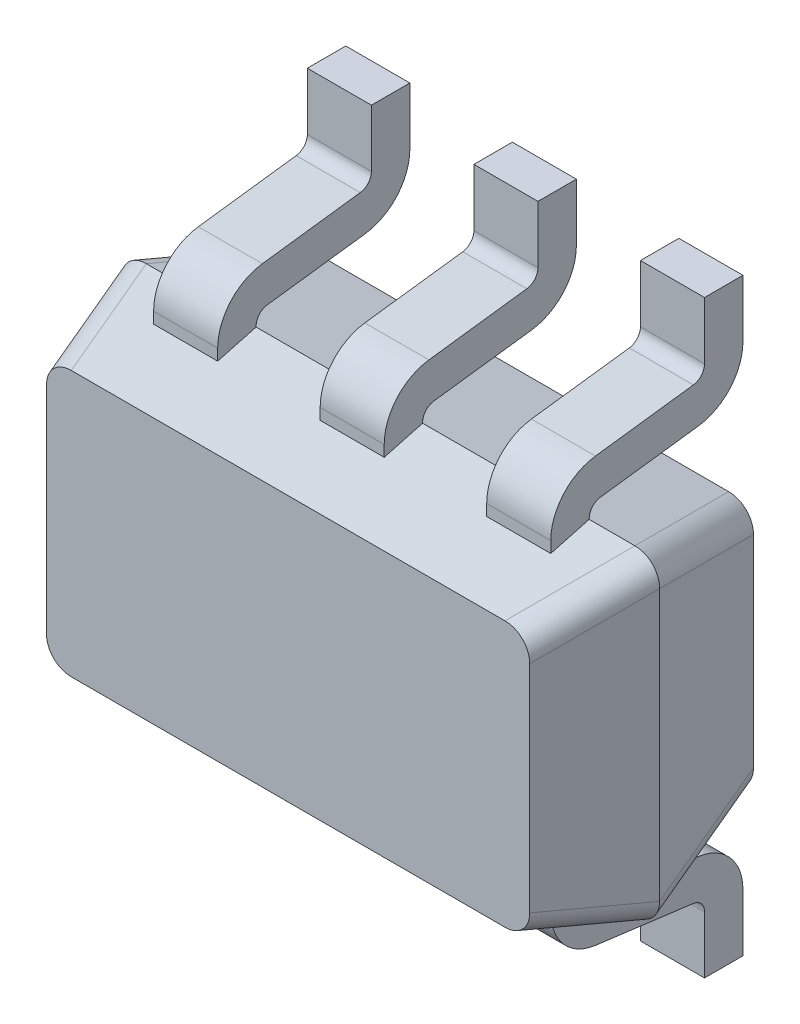
SolidWorks part; units mm, degrees
note: The reader was unsure of these and kept them because the rebuilt part matched: shared geometry of "Эскиз2<4>".
ref_plane "Спереди" through (0, 0, 0) normal (0, 0, 1) x (1, 0, 0)
ref_plane "Сверху" through (0, 0, 0) normal (0, 1, 0) x (1, 0, 0)
ref_plane "Справа" through (0, 0, 0) normal (1, 0, 0) x (0, 0, -1)
sketch "Эскиз1" plane through (0, 0, 0) normal (0, 0, 1) x (1, 0, 0)
  line L1 (-1.05, 0.625) -> (1.05, 0.625)
  line L2 (-1.05, 0.625) -> (-1.05, -0.625)
  line L3 (-1.05, -0.625) -> (1.05, -0.625)
  line L4 (1.05, 0.625) -> (1.05, -0.625)
  point P0 (0, 0)
extrude "Вытянуть1" add sketch "Эскиз1" along normal blind 0.4 draft 15 and the other way blind 0.5 draft 15 from offset 0.6
sketch "Эскиз2" plane through (0, 0, 0) normal (1, 0, 0) x (0, 0, -1)
  line L0 (-0.15, -1.15) -> (0, -1.15)
  line L1 (0, -1.15) -> (0, -0.9259)
  line L2 (-0.75, -0.55) -> (-0.75, -0.6286)
  line L3 (-0.6, -0.6286) -> (-0.6, -0.55)
  line L4 (-0.5564, -0.6782) -> (-0.1744, -0.7275)
  line L5 (-0.15, -1.15) -> (-0.15, -0.9259)
  line L6 (-0.5756, -0.827) -> (-0.1936, -0.8763)
  line L7 (-0.6, -0.625) -> (-0.6, 0.625) construction
  line L8 (-0.6, -0.55) -> (-0.75, -0.55)
  line L9 (0.1932, 0) -> (-1.2427, 0) construction
  line L10 (-0.6, 0.55) -> (-0.75, 0.55)
  line L11 (-0.5756, 0.827) -> (-0.1936, 0.8763)
  line L12 (-0.15, 1.15) -> (-0.15, 0.9259)
  line L13 (-0.5564, 0.6782) -> (-0.1744, 0.7275)
  line L14 (-0.6, 0.6286) -> (-0.6, 0.55)
  line L15 (-0.75, 0.55) -> (-0.75, 0.6286)
  line L16 (0, 1.15) -> (0, 0.9259)
  line L17 (-0.15, 1.15) -> (0, 1.15)
  arc A0 (-0.1936, -0.8763) -> (-0.15, -0.9259) centre (-0.2, -0.9259) cw
  arc A1 (0, -0.9259) -> (-0.1744, -0.7275) centre (-0.2, -0.9259) ccw
  arc A2 (-0.5756, -0.827) -> (-0.75, -0.6286) centre (-0.55, -0.6286) cw
  arc A3 (-0.6, -0.6286) -> (-0.5564, -0.6782) centre (-0.55, -0.6286) ccw
  arc A4 (-0.6, 0.6286) -> (-0.5564, 0.6782) centre (-0.55, 0.6286) cw
  arc A5 (-0.5756, 0.827) -> (-0.75, 0.6286) centre (-0.55, 0.6286) ccw
  arc A6 (0, 0.9259) -> (-0.1744, 0.7275) centre (-0.2, 0.9259) cw
  arc A7 (-0.1936, 0.8763) -> (-0.15, 0.9259) centre (-0.2, 0.9259) ccw
extrude "Вытянуть4" add sketch "Эскиз2" along normal blind 0.125 and the other way blind 0.125 from offset 0.65 contours L13 A6 L16 L17 L12 A7 L11 A5 L15 L10 L14 A4
extrude "Вытянуть5" add sketch "Эскиз2<4>" along normal blind 0.125 and the other way blind 0.125 from offset 0.65 contours A3 L3 L8 L2 A2 L6 A0 L5 L0 L1 A1 L4
sketch "Эскиз2<4>" plane through (0, 0, 0) normal (1, 0, 0) x (0, 0, -1) same geometry as "Эскиз2"
pattern_linear "Линейный массив2" count 2 spacing 1.3 along (-1, 0, 0) of "Вытянуть5"
pattern_linear "Линейный массив3" count 3 spacing 0.65 along (-1, 0, 0) of "Вытянуть4"
fillet "Скругление3" radius 0.1 8 edges at (0.9964, -0.5714, 0.8) (0.9964, 0.5714, 0.8) (-0.9964, 0.5714, 0.8) (-0.9964, -0.5714, 0.8) (0.983, -0.558, 0.35) (-0.983, -0.558, 0.35) (-0.983, 0.558, 0.35) (0.983, 0.558, 0.35)
